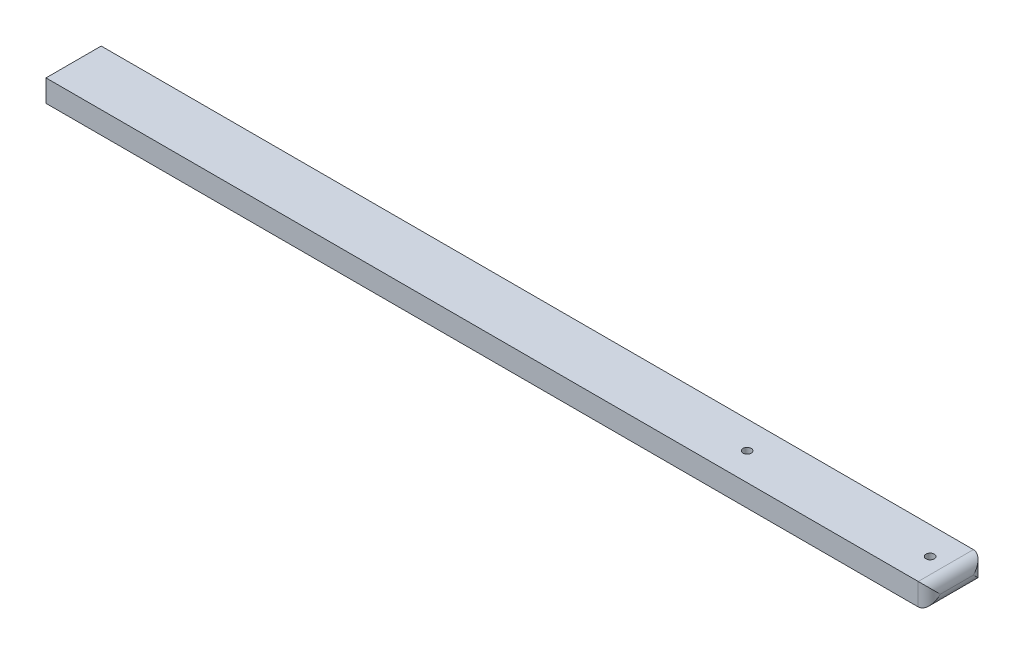
SolidWorks part; units mm, degrees
ref_plane "Front" through (0, 0, 0) normal (0, 0, 1) x (1, 0, 0)
ref_plane "Top" through (0, 0, 0) normal (0, 1, 0) x (1, 0, 0)
ref_plane "Right" through (0, 0, 0) normal (1, 0, 0) x (0, 0, -1)
sketch "Эскиз2" plane through (0, 0, 0) normal (0, 1, 0) x (1, 0, 0)
  line L1 (-80, 5) -> (80, 5)
  line L2 (-80, 5) -> (-80, -5)
  line L3 (-80, -5) -> (80, -5)
  line L4 (80, 5) -> (80, -5)
  line L5 (-80, 5) -> (80, -5) construction
  line L6 (-80, -5) -> (80, 5) construction
  point P0 (0, 0)
  dimension "D1" = 160
  dimension "D2" = 10
extrude "Бобышка-Вытянуть1" add sketch "Эскиз2" along normal blind 4
sketch "Эскиз3" plane through (0, 4, 0) normal (0, 1, 0) x (1, 0, 0)
  line L0 (-80, 0) -> (80, 0) construction
  line L1 (-80, 5) -> (-80, -5) construction
  line L2 (80, -5) -> (80, 5) construction
  circle A0 centre (75.16, 0) radius 0.75
  circle A1 centre (42, 0) radius 0.75
  point P10 (0, 0)
  point P11 (0, 0)
  point P12 (41.7684, -6.6727)
  point P13 (0, 0)
  dimension "D1" = 1.5
  dimension "D2" = 1.5
  dimension "D3" = 33.16
  dimension "D4" = 38
extrude "Вырез-Вытянуть1" cut sketch "Эскиз3" against normal blind 14
fillet "Скругление1" radius 2 4 edges at (80, 2, 5) (80, 2, -5) (80, 0, 0) (80, 4, 0)
